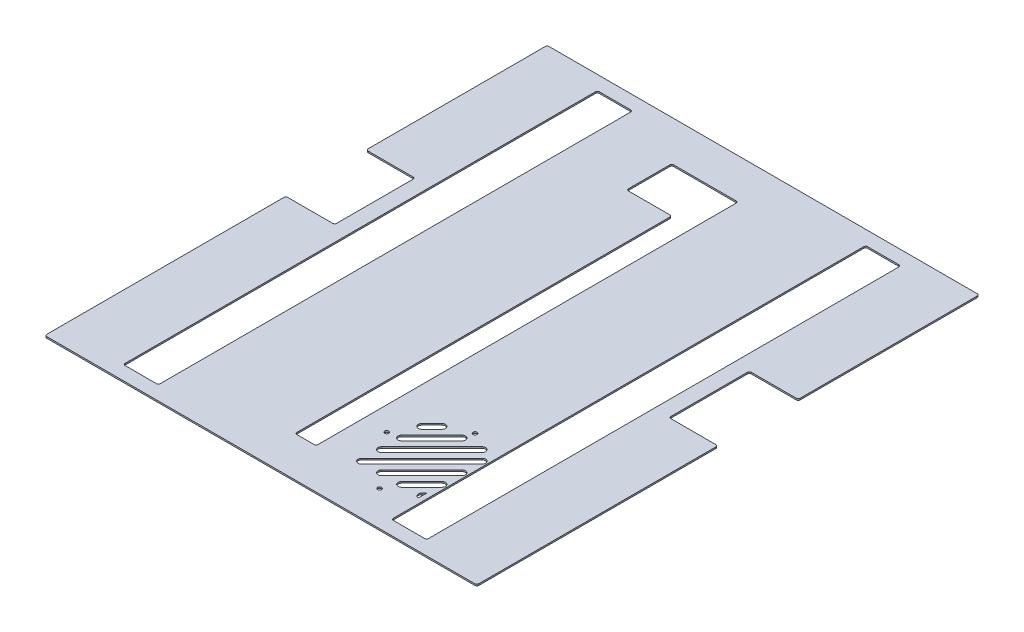
SolidWorks part; units mm, degrees
ref_plane "Front Plane" through (0, 0, 0) normal (0, 0, 1) x (1, 0, 0)
ref_plane "Top Plane" through (0, 0, 0) normal (0, 1, 0) x (1, 0, 0)
ref_plane "Right Plane" through (0, 0, 0) normal (1, 0, 0) x (0, 0, -1)
sketch "Sketch1" plane through (0, 0, 0) normal (0, 1, 0) x (1, 0, 0)
  line L1 (5911.0841, -8452.3124) -> (6341.0841, -8452.3124)
  line L2 (5911.0841, -8452.3124) -> (5911.0841, -8952.3124)
  line L3 (5911.0841, -8952.3124) -> (6341.0841, -8952.3124)
  line L4 (6341.0841, -8452.3124) -> (6341.0841, -8952.3124)
  dimension "D1" = 500
  dimension "D2" = 430
extrude "Boss-Extrude1" add sketch "Sketch1" along normal blind 1.5
sketch "Sketch2" plane through (0, 1.5, 0) normal (0, 1, 0) x (1, 0, 0)
  line L0 (5911.0841, -8452.3124) -> (5911.0841, -8952.3124) construction
  line L1 (5959.6841, -8712.448) -> (5911.0841, -8712.448)
  line L2 (5959.6841, -8712.448) -> (5959.6841, -8632.448)
  line L3 (5959.6841, -8632.448) -> (5911.0841, -8632.448)
  line L4 (5911.0841, -8712.448) -> (5911.0841, -8632.448)
  line L9 (6341.0841, -8952.3124) -> (6341.0841, -8452.3124) construction
  line L10 (6341.0841, -8712.448) -> (6292.4841, -8712.448)
  line L11 (6341.0841, -8712.448) -> (6341.0841, -8632.448)
  line L12 (6341.0841, -8632.448) -> (6292.4841, -8632.448)
  line L13 (6292.4841, -8712.448) -> (6292.4841, -8632.448)
  dimension "D1" = 48.6
  dimension "D2" = 80
  dimension "D3" = 80
  dimension "D4" = 48.6
extrude "Cut-Extrude1" cut sketch "Sketch2" against normal blind 10
sketch "Sketch3" plane through (0, 1.5, 0) normal (0, 1, 0) x (1, 0, 0)
  line L0 (5975.0841, -8541.6519) -> (5975.0841, -8938.3124)
  line L1 (6277.0841, -8938.3124) -> (6242.0841, -8938.3124)
  line L2 (6277.0841, -8938.3124) -> (6277.0841, -8466.3124)
  line L3 (6277.0841, -8466.3124) -> (6242.0841, -8466.3124)
  line L4 (6242.0841, -8938.3124) -> (6242.0841, -8466.3124)
  line L5 (5975.0841, -8466.3124) -> (6010.0841, -8466.3124)
  line L11 (5975.0841, -8938.3124) -> (6010.0841, -8938.3124)
  line L12 (6010.0841, -8466.3124) -> (6010.0841, -8938.3124)
  line L36 (5911.0841, -8712.448) -> (5911.0841, -8952.3124) construction
  line L37 (6341.0841, -8952.3124) -> (6341.0841, -8712.448) construction
  line L39 (6111.0841, -8492.3124) -> (6141.0841, -8492.3124)
  line L40 (6120.0841, -8537.3124) -> (6120.0841, -8912.3124)
  line L41 (6120.0841, -8912.3124) -> (6141.0841, -8912.3124)
  line L42 (6141.0841, -8492.3124) -> (6141.0841, -8912.3124)
  line L44 (6341.0841, -8452.3124) -> (5911.0841, -8452.3124) construction
  line L45 (5975.0841, -8466.3124) -> (5975.0841, -8541.6519)
  line L47 (5911.0841, -8952.3124) -> (6341.0841, -8952.3124) construction
  line L48 (6111.0841, -8492.3124) -> (6075.0841, -8492.3124)
  line L50 (6120.0841, -8537.3124) -> (6075.0841, -8537.3124)
  line L51 (6075.0841, -8492.3124) -> (6075.0841, -8537.3124)
  point P32 (6126.0841, -8452.3124)
  point P33 (6126.0841, -8492.3124)
  dimension "D15" = 40
  dimension "D22" = 45
  dimension "D1" = 35
  dimension "D2" = 472
  dimension "D3" = 35
  dimension "D4" = 472
  dimension "D6" = 64
  dimension "D7" = 45
  dimension "D8" = 64
  dimension "D10" = 420
  dimension "D11" = 110
  dimension "D20" = 14
  dimension "D21" = 14
extrude "Cut-Extrude2" cut sketch "Sketch3" against normal blind 10
sketch "Sketch4" plane through (0, 1.5, 0) normal (0, 1, 0) x (1, 0, 0)
  line L0 (6237.0841, -8848.0965) -> (6237.0841, -8858.0965) construction
  line L1 (6237.0841, -8898.0965) -> (6207.0841, -8898.0965) construction
  line L3 (6237.0841, -8833.0965) -> (6192.0841, -8833.0965) construction
  line L4 (6177.0841, -8898.0965) -> (6177.0841, -8848.0965) construction
  line L5 (5911.0841, -8952.3124) -> (6341.0841, -8952.3124) construction
  line L6 (6177.0841, -8898.0965) -> (6234.5841, -8840.5965)
  line L7 (6179.5841, -8885.5965) -> (6229.5841, -8835.5965)
  line L8 (6174.5841, -8880.5965) -> (6222.0841, -8833.0965)
  line L9 (6177.0841, -8898.0965) -> (6174.5841, -8900.5965)
  line L10 (6174.5841, -8880.5965) -> (6222.0841, -8833.0965)
  line L11 (6179.5841, -8865.5965) -> (6209.5841, -8835.5965)
  line L12 (6177.0841, -8898.0965) -> (6174.5841, -8900.5965) construction
  line L13 (6179.5841, -8865.5965) -> (6209.5841, -8835.5965)
  line L14 (6174.5841, -8860.5965) -> (6204.5841, -8830.5965)
  line L15 (6237.0841, -8888.0965) -> (6239.5841, -8885.5965)
  line L16 (6174.5841, -8860.5965) -> (6204.5841, -8830.5965)
  line L17 (6179.5841, -8845.5965) -> (6189.5841, -8835.5965)
  line L18 (6174.5841, -8840.5965) -> (6184.5841, -8830.5965)
  line L19 (6179.5841, -8885.5965) -> (6229.5841, -8835.5965)
  line L20 (6177.0841, -8878.0965) -> (6222.0841, -8833.0965)
  line L21 (6179.5841, -8865.5965) -> (6209.5841, -8835.5965)
  line L22 (6187.0841, -8898.0965) -> (6237.0841, -8848.0965)
  line L23 (6197.0841, -8898.0965) -> (6234.5841, -8860.5965)
  line L24 (6207.0841, -8898.0965) -> (6237.0841, -8868.0965)
  line L25 (6194.5841, -8900.5965) -> (6234.5841, -8860.5965)
  line L26 (6199.5841, -8905.5965) -> (6237.0841, -8868.0965)
  line L27 (6214.5841, -8900.5965) -> (6234.5841, -8880.5965)
  line L28 (6199.5841, -8905.5965) -> (6237.0841, -8868.0965)
  line L29 (6214.5841, -8900.5965) -> (6234.5841, -8880.5965)
  line L30 (6219.5841, -8905.5965) -> (6237.0841, -8888.0965)
  line L31 (6214.5841, -8900.5965) -> (6234.5841, -8880.5965)
  line L32 (6219.5841, -8905.5965) -> (6237.0841, -8888.0965)
  line L33 (6234.5841, -8900.5965) -> (6237.0841, -8898.0965)
  line L34 (6179.5841, -8905.5965) -> (6237.0841, -8848.0965)
  line L35 (6194.5841, -8900.5965) -> (6234.5841, -8860.5965)
  line L36 (6199.5841, -8905.5965) -> (6237.0841, -8868.0965)
  line L37 (6182.0841, -8833.0965) -> (6192.0841, -8833.0965) construction
  line L38 (6182.0841, -8833.0965) -> (6177.0841, -8833.0965) construction
  line L39 (6177.0841, -8863.0965) -> (6237.0841, -8863.0965) construction
  line L40 (6177.0841, -8838.0965) -> (6177.0841, -8833.0965) construction
  line L41 (6177.0841, -8838.0965) -> (6177.0841, -8848.0965) construction
  line L42 (6197.0841, -8898.0965) -> (6177.0841, -8898.0965) construction
  line L43 (6179.5841, -8865.5965) -> (6209.5841, -8835.5965)
  line L44 (6174.5841, -8860.5965) -> (6204.5841, -8830.5965)
  line L45 (6179.5841, -8845.5965) -> (6189.5841, -8835.5965)
  line L46 (6147.0841, -8878.0965) -> (6157.0841, -8868.0965) [skipped]
  line L47 (6147.0841, -8898.0965) -> (6157.0841, -8888.0965) [skipped]
  line L48 (6147.0841, -8888.0965) -> (6157.0841, -8878.0965) [skipped]
  line L49 (6237.0841, -8868.0965) -> (6239.5841, -8865.5965)
  line L52 (6222.0841, -8833.0965) -> (6224.5841, -8830.5965)
  line L54 (6237.0841, -8833.0965) -> (6237.0841, -8839.561) construction
  line L55 (6237.0841, -8898.0965) -> (6237.0841, -8906.6321)
  line L57 (6237.0841, -8888.0965) -> (6237.0841, -8898.0965) construction
  line L59 (6237.0841, -8848.0965) -> (6239.5841, -8845.5965)
  line L60 (6237.0841, -8868.0965) -> (6237.0841, -8879.561) construction
  arc A1 (6189.5841, -8835.5965) -> (6184.5841, -8830.5965) centre (6187.0841, -8833.0965) ccw
  arc A2 (6209.5841, -8835.5965) -> (6204.5841, -8830.5965) centre (6207.0841, -8833.0965) ccw
  arc A3 (6229.5841, -8835.5965) -> (6224.5841, -8830.5965) centre (6227.0841, -8833.0965) ccw
  arc A5 (6174.5841, -8840.5965) -> (6179.5841, -8845.5965) centre (6177.0841, -8843.0965) ccw
  arc A6 (6174.5841, -8860.5965) -> (6179.5841, -8865.5965) centre (6177.0841, -8863.0965) ccw
  arc A7 (6174.5841, -8880.5965) -> (6179.5841, -8885.5965) centre (6177.0841, -8883.0965) ccw
  arc A8 (6174.5841, -8900.5965) -> (6179.5841, -8905.5965) centre (6177.0841, -8903.0965) ccw
  arc A9 (6194.5841, -8900.5965) -> (6199.5841, -8905.5965) centre (6197.0841, -8903.0965) ccw
  arc A10 (6214.5841, -8900.5965) -> (6219.5841, -8905.5965) centre (6217.0841, -8903.0965) ccw
  arc A11 (6234.5841, -8900.5965) -> (6237.0841, -8906.6321) centre (6237.0841, -8903.0965) ccw
  arc A12 (6249.5841, -8835.5965) -> (6244.5841, -8830.5965) centre (6247.0841, -8833.0965) ccw [skipped]
  arc A13 (6239.5841, -8845.5965) -> (6234.5841, -8840.5965) centre (6237.0841, -8843.0965) ccw
  arc A14 (6239.5841, -8865.5965) -> (6234.5841, -8860.5965) centre (6237.0841, -8863.0965) ccw
  arc A15 (6239.5841, -8885.5965) -> (6234.5841, -8880.5965) centre (6237.0841, -8883.0965) ccw
  line M5 (6242.0841, -8938.3124) -> (6242.0841, -8466.3124)
  dimension "D8" = 4
  dimension "D1" = 65
  dimension "D3" = 54.2159
  dimension "D4" = 4
  dimension "D5" = 4
  dimension "D6" = 4
  dimension "D7" = 4
  dimension "D9" = 4
  dimension "D10" = 4
extrude "Cut-Extrude3" cut sketch "Sketch4" against normal blind 10 contours L27 A10 L30 M5 | L25 A9 L26 L24 L23 M5 | L8 A7 L7 A3 L52 L10 | L14 A6 L11 A2 | L18 A5 L17 A1 | L33 A11 M5 | L59 A13 L6 L9 A8 L34 region at (6202.0841, 1.5, 8858.0965) region at (6192.0841, 1.5, 8848.0965) region at (6227.0841, 1.5, 8893.0965) region at (6182.0841, 1.5, 8838.0965) region at (6217.0841, 1.5, 8883.0965) region at (6235.6369, 1.5, 8902.8482)
fillet "Fillet2" radius 2 12 edges at (6292.4841, 0.75, 8632.448) (6341.0841, 0.75, 8632.448) (6341.0841, 0.75, 8712.448) (6292.4841, 0.75, 8712.448) (5959.6841, 0.75, 8632.448) (5959.6841, 0.75, 8712.448) (5911.0841, 0.75, 8712.448) (5911.0841, 0.75, 8632.448) (5911.0841, 0.75, 8452.3124) (6341.0841, 0.75, 8452.3124) (6341.0841, 0.75, 8952.3124) (5911.0841, 0.75, 8952.3124)
fillet "Fillet3" radius 2 14 edges at (6010.0841, 0.75, 8938.3124) (5975.0841, 0.75, 8938.3124) (6010.0841, 0.75, 8466.3124) (5975.0841, 0.75, 8466.3124) (6277.0841, 0.75, 8938.3124) (6242.0841, 0.75, 8938.3124) (6277.0841, 0.75, 8466.3124) (6242.0841, 0.75, 8466.3124) (6141.0841, 0.75, 8912.3124) (6120.0841, 0.75, 8912.3124) (6141.0841, 0.75, 8492.3124) (6120.0841, 0.75, 8537.3124) (6075.0841, 0.75, 8492.3124) (6075.0841, 0.75, 8537.3124)
sketch "Sketch6" plane through (0, 1.5, 0) normal (0, 1, 0) x (1, 0, 0)
  line L0 (6177.0841, -8833.0965) -> (6242.0841, -8833.0965) construction
  line L1 (6242.0841, -8468.3124) -> (6242.0841, -8936.3124) construction
  line L2 (6242.0841, -8833.0965) -> (6242.0841, -8898.0738) construction
  line L3 (6242.0841, -8898.0738) -> (6177.0841, -8898.0965) construction
  line L4 (6177.0841, -8898.0965) -> (6177.0841, -8833.0965) construction
  line L5 (6177.0841, -8865.5965) -> (6242.0841, -8865.5852) construction
  line L6 (6209.5841, -8833.0965) -> (6209.5841, -8898.0852) construction
  line L7 (6209.5841, -8833.0965) -> (6209.5841, -8822.5908) construction
  line L8 (6177.0841, -8865.5965) -> (6164.5841, -8865.5965) construction
  line L9 (6209.5841, -8898.0852) -> (6209.5841, -8917.5908) construction
  line L10 (6237.0841, -8833.0965) -> (6237.0841, -8839.561) construction
  circle A0 centre (6209.5841, -8822.5908) radius 2
  circle A1 centre (6209.5841, -8917.5908) radius 2
  circle A2 centre (6164.5841, -8865.5965) radius 2
  point P16 (0, 0)
  point P20 (0, 0)
  point P21 (0, 0)
  dimension "D1" = 4
  dimension "D2" = 4
  dimension "D3" = 4
  dimension "D4" = 95
  dimension "D5" = 43
  dimension "D6" = 45
  dimension "D7" = 27.5
extrude "Cut-Extrude4" cut sketch "Sketch6" against normal blind 10
